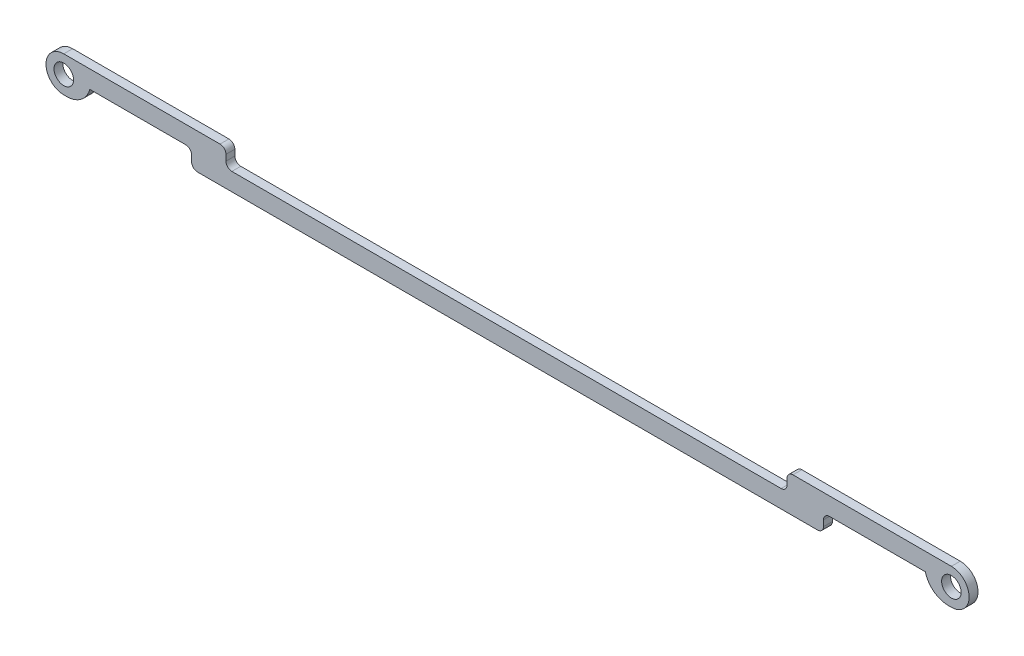
SolidWorks part; units mm, degrees
ref_plane "前视基准面" through (0, 0, 0) normal (0, 0, 1) x (1, 0, 0)
ref_plane "上视基准面" through (0, 0, 0) normal (0, 1, 0) x (1, 0, 0)
ref_plane "右视基准面" through (0, 0, 0) normal (1, 0, 0) x (0, 0, -1)
sketch "草图1" plane through (0, 0, 0) normal (0, 0, 1) x (1, 0, 0)
  line L0 (0, 0) -> (500, 0) construction
  line L1 (0, 10) -> (500, 10)
  line L2 (0, -10) -> (500, -10)
  arc A0 (0, 10) -> (0, -10) centre (0, 0) ccw
  arc A1 (500, -10) -> (500, 10) centre (500, 0) ccw
  circle A2 centre (0, 0) radius 5.5
  circle A3 centre (500, 0) radius 5.5
  point P3 (250, 0)
  dimension "D1" = 10
  dimension "D3" = 11
  dimension "D2" = 500
extrude "凸台-拉伸1" add sketch "草图1" along normal blind 5
scale "缩放比例1" scale about origin uniform scaling yes scale factor 0.3
sketch "草图3" plane through (0, 0, 1.5) normal (0, 0, 1) x (1, 0, 0)
  line L0 (75, 3) -> (75, 29.7209) construction
  line L1 (4.3978, -5.4379) -> (21.6079, -5.4379)
  line L2 (4.3978, -5.4379) -> (4.3978, 0)
  line L3 (4.3978, 0) -> (21.6079, 0)
  line L4 (21.6079, -5.4379) -> (21.6079, 0)
  line L5 (150, 3) -> (0, 3) construction
  line L6 (128.3921, -5.4379) -> (128.3921, 0)
  line L7 (145.6022, 0) -> (128.3921, 0)
  line L8 (145.6022, -5.4379) -> (145.6022, 0)
  line L9 (145.6022, -5.4379) -> (128.3921, -5.4379)
extrude "切除-拉伸2" cut sketch "草图3" against normal blind 20
fillet "圆角1" radius 4 2 edges at (145.6022, -3, 0.75) (4.3978, -3, 0.75)
fillet "圆角2" radius 1 4 edges at (21.6079, -3, 0.75) (21.6079, 0, 0.75) (128.3921, 0, 0.75) (128.3921, -3, 0.75)
sketch "草图4" plane through (0, 0, 1.5) normal (0, 0, 1) x (1, 0, 0)
  line L1 (27.4132, 9.5487) -> (122.2306, 9.5487)
  line L2 (27.4132, 9.5487) -> (27.4132, 0)
  line L3 (27.4132, 0) -> (122.2306, 0)
  line L4 (122.2306, 9.5487) -> (122.2306, 0)
extrude "切除-拉伸3" cut sketch "草图4" against normal blind 20
fillet "圆角3" radius 1 4 edges at (122.2306, 0, 0.75) (122.2306, 3, 0.75) (27.4132, 3, 0.75) (27.4132, 0, 0.75)
